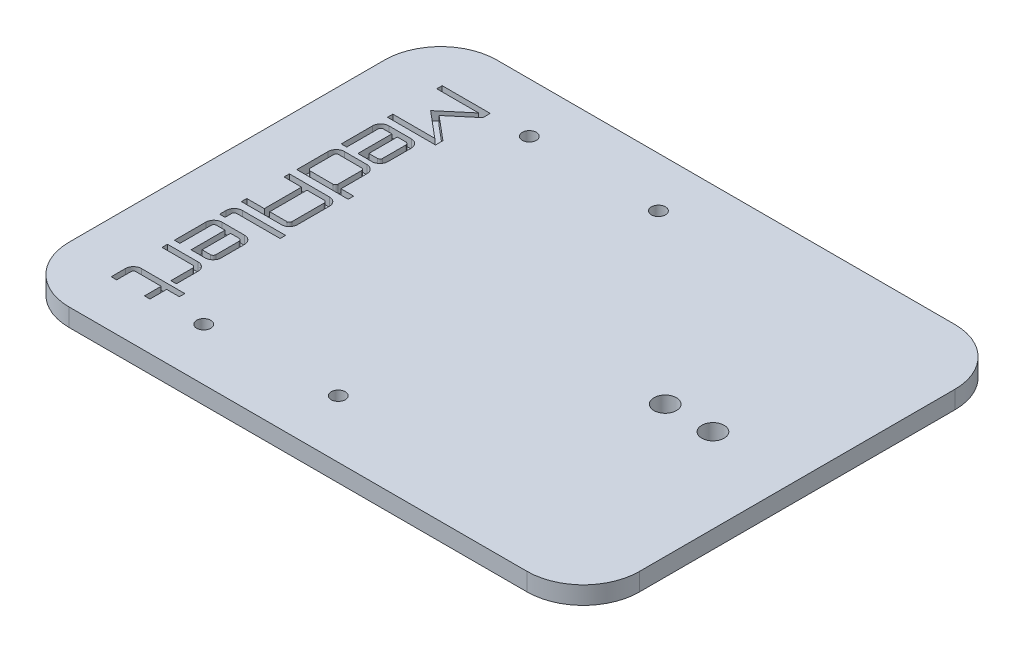
SolidWorks part; units mm, degrees
ref_plane "Front Plane" through (0, 0, 0) normal (0, 0, 1) x (1, 0, 0)
ref_plane "Top Plane" through (0, 0, 0) normal (0, 1, 0) x (1, 0, 0)
ref_plane "Right Plane" through (0, 0, 0) normal (1, 0, 0) x (0, 0, -1)
sketch "Sketch1" plane through (0, 0, 0) normal (0, 1, 0) x (1, 0, 0)
  line L1 (50.8, -38.1) -> (-50.8, -38.1)
  line L2 (50.8, -38.1) -> (50.8, 38.1)
  line L3 (50.8, 38.1) -> (-50.8, 38.1)
  line L4 (-50.8, -38.1) -> (-50.8, 38.1)
  line L5 (50.8, -38.1) -> (-50.8, 38.1) construction
  line L6 (50.8, 38.1) -> (-50.8, -38.1) construction
  point P0 (0, 0)
  dimension "D1" = 101.6
  dimension "D2" = 76.2
extrude "Boss-Extrude1" add sketch "Sketch1" along normal blind 3.175
sketch "Sketch2" plane through (0, 3.175, 0) normal (0, 1, 0) x (1, 0, 0)
  line L0 (-2.2581, 0) -> (2.2581, 0) construction
  line L1 (50.8, -38.1) -> (50.8, 38.1) construction
  circle A0 centre (35.8, 0) radius 2
  circle A1 centre (27.291, 0) radius 2
  dimension "D1" = 4
  dimension "D2" = 4
  dimension "D3" = 8.509
  dimension "D4" = 15
extrude "Cut-Extrude1" cut sketch "Sketch2" against normal through all
fillet "Fillet1" radius 10 4 edges at (-50.8, 1.5875, -38.1) (-50.8, 1.5875, 38.1) (50.8, 1.5875, 38.1) (50.8, 1.5875, -38.1)
sketch "Sketch4" plane through (0, 3.175, 0) normal (0, 1, 0) x (1, 0, 0)
  circle A0 centre (-3.1344, 29.2185) radius 1.25
  circle A1 centre (-3.1344, -27.8181) radius 1.25
  circle A2 centre (-26.1344, 29.2185) radius 1.25
  circle A3 centre (-26.1344, -28.7815) radius 1.25
  dimension "D1" = 2.5
  dimension "D2" = 2.5
  dimension "D3" = 2.5
  dimension "D4" = 2.5
  dimension "D5" = 23
  dimension "D6" = 23
  dimension "D7" = 58
extrude "Cut-Extrude2" cut sketch "Sketch4" against normal through all
sketch "Sketch5" plane through (0, 3.175, 0) normal (0, 1, 0) x (1, 0, 0)
  line L1 (-41.7142, 38.1) -> (-41.7142, -38.1) construction
  line L2 (40.8, 38.1) -> (-40.8, 38.1) construction
  line L3 (-40.8, -38.1) -> (40.8, -38.1) construction
  text T0 "MedAlert" font "Orbitron" height in points 24
extrude "Cut-Extrude3" cut sketch "Sketch5" against normal blind 1.5875
